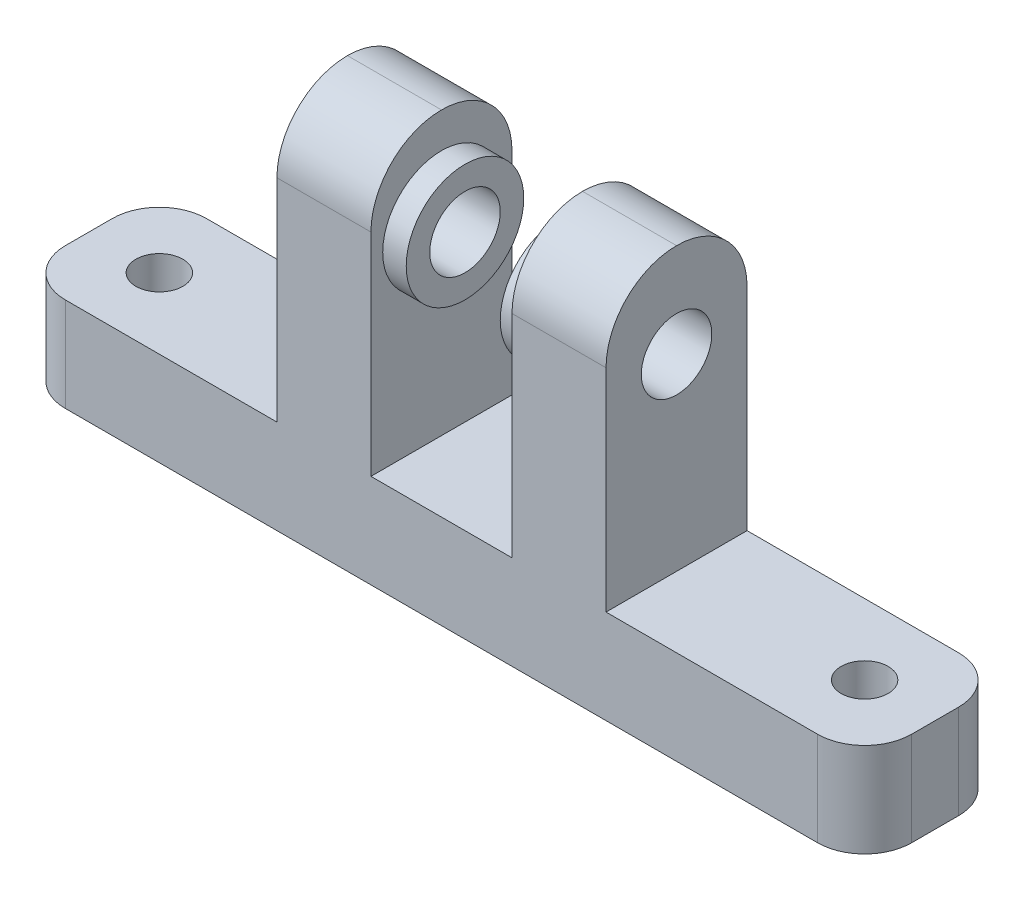
SolidWorks part; units mm, degrees
ref_plane "Front Plane" through (0, 0, 0) normal (0, 0, 1) x (1, 0, 0)
ref_plane "Top Plane" through (0, 0, 0) normal (0, 1, 0) x (1, 0, 0)
ref_plane "Right Plane" through (0, 0, 0) normal (1, 0, 0) x (0, 0, -1)
sketch "Sketch2" plane through (0, 0, 0) normal (0, 1, 0) x (1, 0, 0)
  line L1 (-7, 3) -> (7, 3)
  line L2 (-7, 3) -> (-7, -3)
  line L3 (-7, -3) -> (7, -3)
  line L4 (7, 3) -> (7, -3)
  line L5 (-7, 3) -> (7, -3) construction
  line L6 (-7, -3) -> (7, 3) construction
  point P0 (0, 0)
extrude "Boss-Extrude1" add sketch "Sketch2" along normal blind 4
sketch "Sketch3" plane through (0, 4, 0) normal (0, 1, 0) x (1, 0, 0)
  line L0 (-7, -3) -> (-3, -3)
  line L1 (-7, -3) -> (7, -3) construction
  line L2 (-3, -3) -> (-3, 3)
  line L3 (7, 3) -> (-7, 3) construction
  line L4 (-3, 3) -> (-7, 3)
  line L5 (-7, 3) -> (-7, -3)
  line L6 (7, -3) -> (3, -3)
  line L7 (3, -3) -> (3, 3)
  line L8 (3, 3) -> (7, 3)
  line L9 (7, 3) -> (7, -3)
extrude "Boss-Extrude2" add sketch "Sketch3" along normal blind 12
sketch "Sketch4" plane through (7, 0, 0) normal (1, 0, 0) x (0, 0, -1)
  circle A0 centre (0, 12) radius 1.5
extrude "Cut-Extrude1" cut sketch "Sketch4" against normal through all both and the other way through all
sketch "Sketch5" plane through (-3, 0, 0) normal (1, 0, 0) x (0, 0, -1)
  circle A0 centre (0, 12) radius 1.5
  circle A1 centre (0, 12) radius 2.5
extrude "Boss-Extrude3" add sketch "Sketch5" along normal blind 1
sketch "Sketch6" plane through (3, 0, 0) normal (-1, 0, 0) x (0, 0, 1)
  circle A0 centre (0, 12) radius 1.5
  circle A1 centre (0, 12) radius 2.5
extrude "Boss-Extrude4" add sketch "Sketch6" along normal blind 1
sketch "Sketch7" plane through (0, 4, 0) normal (0, 1, 0) x (1, 0, 0)
  line L2 (18, 3) -> (18, -3)
  line L3 (18, -3) -> (7, -3)
  line L4 (-7, -3) -> (-7, 3)
  line L5 (-7, 3) -> (-7, -3) construction
  line L6 (-7, 3) -> (-18, 3)
  line L7 (-18, 3) -> (-18, -3)
  line L8 (-18, -3) -> (-7, -3)
  line L9 (18, 3) -> (7, 3)
  line L10 (7, 3) -> (7, -3)
  circle A2 centre (-15, 0) radius 1
  circle A3 centre (15, 0) radius 1
extrude "Boss-Extrude5" add sketch "Sketch7" against normal blind 4
fillet "Fillet1" radius 2 4 edges at (-18, 2, -3) (-18, 2, 3) (18, 2, 3) (18, 2, -3)
fillet "Fillet2" radius 3 4 edges at (-5, 16, -3) (5, 16, -3) (5, 16, 3) (-5, 16, 3)
